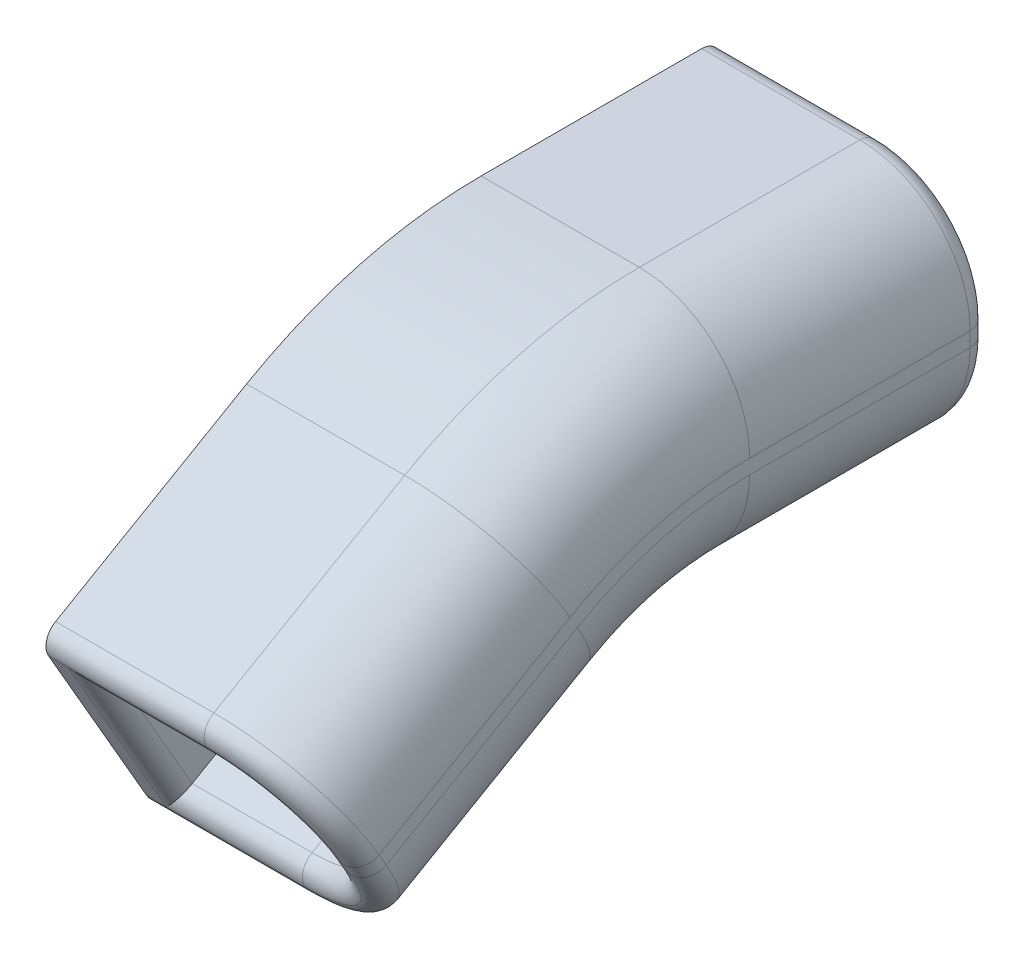
SolidWorks part; units mm, degrees
ref_plane "Front Plane" through (0, 0, 0) normal (0, 0, 1) x (1, 0, 0)
ref_plane "Top Plane" through (0, 0, 0) normal (0, 1, 0) x (1, 0, 0)
ref_plane "Right Plane" through (0, 0, 0) normal (1, 0, 0) x (0, 0, -1)
sketch "Sketch1" plane through (0, 0, 0) normal (0, 0, 1) x (1, 0, 0)
  line L0 (-5.6, 4.9) -> (1, 4.9)
  line L1 (2.6558, 0) -> (1.3279, 2.3)
  line L2 (1.3279, 2.3) -> (-1.3279, 2.3)
  line L3 (-1.3279, 2.3) -> (-2.6558, 0)
  line L4 (-2.6558, 0) -> (-1.3279, -2.3)
  line L5 (-1.3279, -2.3) -> (1.3279, -2.3)
  line L6 (1.3279, -2.3) -> (2.6558, 0)
  line L7 (-4, 3.3) -> (1, 3.3) construction
  line L8 (-4, 3.3) -> (-4, -3.3) construction
  line L9 (-4, -3.3) -> (1, -3.3) construction
  line L10 (4, 0.3) -> (4, -0.3) construction
  line L11 (5.6, 0.3) -> (5.6, -0.3)
  line L12 (-5.6, -4.9) -> (1, -4.9)
  line L13 (-5.6, 4.9) -> (-5.6, -4.9)
  circle A0 centre (0, 0) radius 2.3 construction
  arc A1 (4, -0.3) -> (1, -3.3) centre (1, -0.3) cw construction
  arc A2 (4, 0.3) -> (1, 3.3) centre (1, 0.3) ccw construction
  arc A3 (5.6, 0.3) -> (1, 4.9) centre (1, 0.3) ccw
  arc A4 (5.6, -0.3) -> (1, -4.9) centre (1, -0.3) cw
  point P17 (4, 3.3)
  dimension "D1" = 4.6
  dimension "D6" = 3
  dimension "D2" = 6.6
  dimension "D3" = 1
  dimension "D4" = 8
  dimension "D5" = 4
  dimension "D7" = 1.6
sketch "Sketch2" plane through (0, 0, 0) normal (1, 0, 0) x (0, 0, -1)
  line L0 (0, 0) -> (-10, 0)
  line L1 (-17.3397, -1.9667) -> (-26, -6.9667)
  arc A0 (-10, 0) -> (-17.3397, -1.9667) centre (-10, -14.6795) ccw
  dimension "D3" = 10
  dimension "D1" = 30
  dimension "D2" = 26
sweep "Sweep1" add profiles "Sketch1" path "Sketch2"
sketch "Sketch3" plane through (0, 0, 0) normal (0, 0, -1) x (-1, 0, 0)
  line L0 (4, -3.3) -> (4, 3.3)
  line L1 (4, 3.3) -> (-1, 3.3)
  line L2 (-4, 0.3) -> (-4, -0.3)
  line L3 (-1, -3.3) -> (4, -3.3)
  line L4 (5.6, -4.9) -> (5.6, 4.9)
  line L5 (5.6, 4.9) -> (-1, 4.9)
  line L6 (-5.6, 0.3) -> (-5.6, -0.3)
  line L7 (-1, -4.9) -> (5.6, -4.9)
  line L8 (5.6, -4.9) -> (5.6, 4.9) construction
  line L9 (5.6, 4.9) -> (-1, 4.9) construction
  line L10 (-5.6, 0.3) -> (-5.6, -0.3) construction
  line L11 (-1, -4.9) -> (5.6, -4.9) construction
  arc A0 (-1, 3.3) -> (-4, 0.3) centre (-1, 0.3) ccw
  arc A1 (-4, -0.3) -> (-1, -3.3) centre (-1, -0.3) ccw
  arc A2 (-1, 4.9) -> (-5.6, 0.3) centre (-1, 0.3) ccw
  arc A3 (-5.6, -0.3) -> (-1, -4.9) centre (-1, -0.3) ccw
  arc A4 (-1, 4.9) -> (-5.6, 0.3) centre (-1, 0.3) ccw construction
  arc A5 (-5.6, -0.3) -> (-1, -4.9) centre (-1, -0.3) ccw construction
  dimension "D1" = 0
  dimension "D2" = 1.6
extrude "Cut-Extrude1" cut sketch "Sketch3" against normal blind 10
sketch "Sketch4" plane through (0, -13, 22.5167) normal (0, -0.5, 0.866) x (1, 0, 0)
  line L0 (-4, 10.2667) -> (-4, 3.6667)
  line L1 (-4, 3.6667) -> (1, 3.6667)
  line L2 (4, 6.6667) -> (4, 7.2667)
  line L3 (1, 10.2667) -> (-4, 10.2667)
  line L4 (-5.6, 11.8667) -> (-5.6, 2.0667)
  line L5 (-5.6, 2.0667) -> (1, 2.0667)
  line L6 (5.6, 6.6667) -> (5.6, 7.2667)
  line L7 (1, 11.8667) -> (-5.6, 11.8667)
  line L8 (-5.6, 11.8667) -> (-5.6, 2.0667) construction
  line L9 (-5.6, 2.0667) -> (1, 2.0667) construction
  line L10 (5.6, 6.6667) -> (5.6, 7.2667) construction
  line L11 (1, 11.8667) -> (-5.6, 11.8667) construction
  arc A0 (1, 3.6667) -> (4, 6.6667) centre (1, 6.6667) ccw
  arc A1 (4, 7.2667) -> (1, 10.2667) centre (1, 7.2667) ccw
  arc A2 (1, 2.0667) -> (5.6, 6.6667) centre (1, 6.6667) ccw
  arc A3 (5.6, 7.2667) -> (1, 11.8667) centre (1, 7.2667) ccw
  arc A4 (1, 2.0667) -> (5.6, 6.6667) centre (1, 6.6667) ccw construction
  arc A5 (5.6, 7.2667) -> (1, 11.8667) centre (1, 7.2667) ccw construction
  dimension "D1" = 0
  dimension "D2" = 1.6
extrude "Cut-Extrude2" cut sketch "Sketch4" against normal blind 10
fillet "Fillet1" radius 0.8 22 edges at (-1.5, 3.3, 0) (-1.5, -3.3, 0) (3.1213, -2.4213, 0) (4, 0, 0) (-1.5, -9.8246, 24.35) (3.1213, -9.0636, 24.7893) (4, -6.9667, 26) (3.1213, -4.8698, 27.2107) (-2.3, -4.9, 0) (4.2527, -3.5527, 0) (5.6, 0, 0) (4.2527, 3.5527, 0) (-2.3, -11.2102, 23.55) (4.2527, -10.0434, 24.2237) (5.6, -6.9667, 26) (4.2527, -3.89, 27.7763) (-4, 0, 0) (3.1213, 2.4213, 0) (-4, -6.9667, 26) (-1.5, -4.1088, 27.65) (-2.3, 4.9, 0) (-2.3, -2.7232, 28.45)
